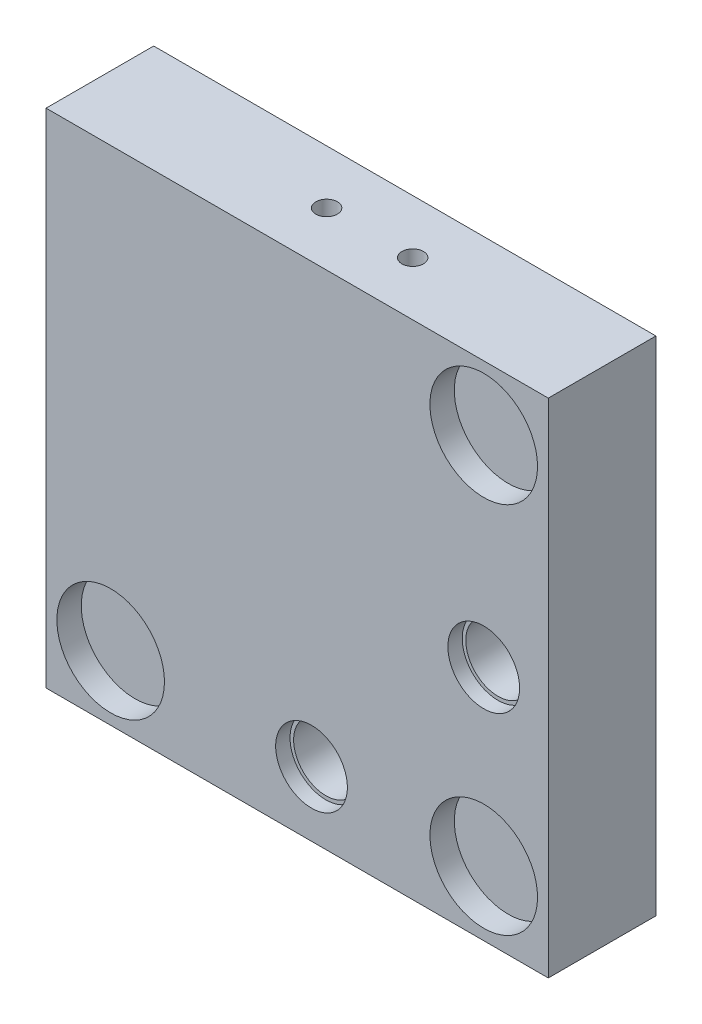
SolidWorks part; units mm, degrees
ref_plane "Front Plane" through (0, 0, 0) normal (0, 0, 1) x (1, 0, 0)
ref_plane "Top Plane" through (0, 0, 0) normal (0, 1, 0) x (1, 0, 0)
ref_plane "Right Plane" through (0, 0, 0) normal (1, 0, 0) x (0, 0, -1)
sketch "Sketch1" plane through (0, 0, 0) normal (0, 0, 1) x (1, 0, 0)
  line L1 (-17.7337, 13.9901) -> (17.2663, 13.9901)
  line L2 (-17.7337, 13.9901) -> (-17.7337, -21.0099)
  line L3 (-17.7337, -21.0099) -> (17.2663, -21.0099)
  line L4 (17.2663, 13.9901) -> (17.2663, -21.0099)
  dimension "D1" = 35
  dimension "D2" = 35
extrude "Boss-Extrude1" add sketch "Sketch1" along normal blind 7.5
sketch "Sketch2" plane through (0, 0, 0) normal (0, 0, -1) x (-1, 0, 0)
  line L0 (17.7337, 2.9901) -> (-6.2663, 2.9901)
  line L1 (17.7337, 13.9901) -> (17.7337, -21.0099) construction
  line L2 (-6.2663, 2.9901) -> (-6.2663, -10.0099)
  line L3 (-6.2663, -10.0099) -> (17.7337, -10.0099)
  line L4 (-17.2663, 13.9901) -> (17.7337, 13.9901) construction
  line L6 (-17.2663, -21.0099) -> (-17.2663, 13.9901) construction
  line L7 (17.7337, 2.9901) -> (17.7337, -10.0099)
  dimension "D1" = 13
  dimension "D2" = 11
  dimension "D3" = 11
extrude "Cut-Extrude2" cut sketch "Sketch2" against normal blind 4
sketch "Sketch4" plane through (0, 0, 7.5) normal (0, 0, 1) x (1, 0, 0)
  line L0 (17.2663, -21.0099) -> (17.2663, 13.9901) construction
  line L1 (-17.7337, -21.0099) -> (17.2663, -21.0099) construction
  line L2 (-17.7337, 13.9901) -> (-17.7337, -21.0099) construction
  line L3 (17.2663, 13.9901) -> (-17.7337, 13.9901) construction
  circle A0 centre (12.7663, -16.5099) radius 3.75
  circle A1 centre (-13.2337, -16.5099) radius 3.75
  circle A2 centre (12.7663, 9.4901) radius 3.75
  dimension "D3" = 7.5
  dimension "D5" = 7.5
  dimension "D7" = 4.5
  dimension "D8" = 4.5
  dimension "D9" = 7.5
  dimension "D1" = 4.5
  dimension "D2" = 4.5
  dimension "D4" = 4.5
  dimension "D6" = 4.5
extrude "Cut-Extrude3" cut sketch "Sketch4" against normal blind 1.7
sketch "Sketch5" plane through (0, 0, 7.5) normal (0, 0, 1) x (1, 0, 0)
  line L0 (-17.7337, -21.0099) -> (17.2663, -21.0099) construction
  line L1 (17.2663, -21.0099) -> (17.2663, 13.9901) construction
  circle A0 centre (12.7663, -4.5099) radius 2.5
  circle A1 centre (0.7663, -16.5099) radius 2.5
  dimension "D5" = 5
  dimension "D6" = 5
  dimension "D1" = 16.5
  dimension "D2" = 16.5
  dimension "D3" = 4.5
  dimension "D4" = 4.5
sketch "Sketch10" plane through (0, 13.9901, 0) normal (0, 1, 0) x (1, 0, 0)
  line L0 (17.2663, -7.5) -> (17.2663, 0) construction
  line L1 (17.2663, 0) -> (-17.7337, 0) construction
  line L2 (17.2663, -7.5) -> (-17.7337, -7.5) construction
  circle A0 centre (4.0663, -3.75) radius 0.75
  circle A1 centre (-1.9337, -3.75) radius 0.75
  dimension "D1" = 13.2
  dimension "D2" = 1.5
  dimension "D3" = 1.5
  dimension "D4" = 3.75
  dimension "D5" = 3.75
  dimension "D6" = 6
extrude "Cut-Extrude7" cut sketch "Sketch10" against normal blind 7
extrude "Cut-Extrude11" cut sketch "Sketch5" against normal blind 1
sketch "Sketch11" plane through (0, 0, 6.5) normal (0, 0, 1) x (1, 0, 0)
  circle A0 centre (0.7663, -16.5099) radius 2.25
  circle A1 centre (12.7663, -4.5099) radius 2.25
  dimension "D1" = 4.5
  dimension "D2" = 4.5
extrude "Cut-Extrude12" cut sketch "Sketch11" against normal blind 5
